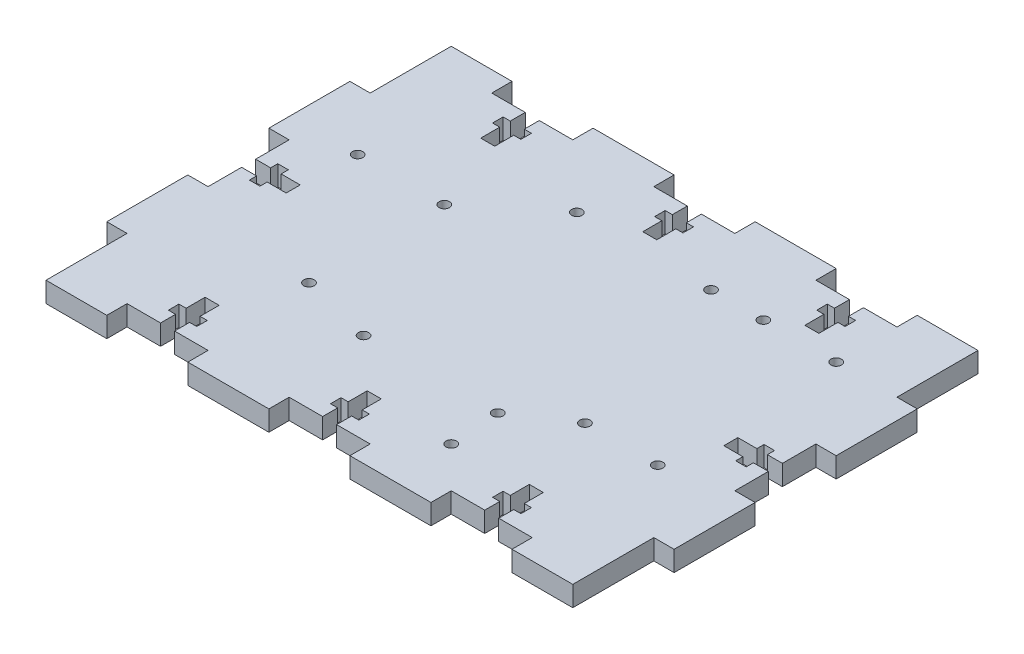
SolidWorks part; units mm, degrees
ref_plane "Front Plane" through (0, 0, 0) normal (0, 0, 1) x (1, 0, 0)
ref_plane "Top Plane" through (0, 0, 0) normal (0, 1, 0) x (1, 0, 0)
ref_plane "Right Plane" through (0, 0, 0) normal (1, 0, 0) x (0, 0, -1)
sketch "Sketch1" plane through (0, 0, 0) normal (0, 1, 0) x (1, 0, 0)
  line L1 (0, 0) -> (177.8, 0)
  line L2 (0, 0) -> (0, 127)
  line L3 (0, 127) -> (177.8, 127)
  line L4 (177.8, 0) -> (177.8, 127)
  dimension "D1" = 127
  dimension "D2" = 177.8
extrude "Boss-Extrude1" add sketch "Sketch1" along normal blind 6.35
sketch "Sketch2" plane through (0, 6.35, 0) normal (0, 1, 0) x (1, 0, 0)
  line L1 (0, 127) -> (6.35, 127)
  line L2 (0, 127) -> (0, 101.6)
  line L3 (0, 101.6) -> (6.35, 101.6)
  line L4 (6.35, 127) -> (6.35, 101.6)
  dimension "D1" = 25.4
  dimension "D2" = 6.35
extrude "Cut-Extrude1" cut sketch "Sketch2" against normal blind 6.35
pattern_linear "LPattern1" count 3 spacing 50.8 along (0, 0, 1) count 2 spacing 171.45 along (1, 0, 0) of "Cut-Extrude1"
sketch "Sketch3" plane through (0, 6.35, 0) normal (0, 1, 0) x (1, 0, 0)
  line L0 (6.35, 0) -> (171.45, 0) construction
  line L1 (25.4, 0) -> (50.8, 0)
  line L2 (25.4, 0) -> (25.4, 6.35)
  line L3 (25.4, 6.35) -> (50.8, 6.35)
  line L4 (50.8, 0) -> (50.8, 6.35)
  line L5 (0, 50.8) -> (0, 25.4) construction
  dimension "D1" = 25.4
  dimension "D2" = 6.35
  dimension "D3" = 25.4
extrude "Cut-Extrude2" cut sketch "Sketch3" against normal blind 6.35
pattern_linear "LPattern2" count 3 spacing 50.8 along (1, 0, 0) count 2 spacing 120.65 along (0, 0, -1) of "Cut-Extrude2"
ref_plane "Plane1" through (0, 0, -63.5) normal (0, 0, 1) x (1, 0, 0)
ref_plane "Plane2" through (88.9, 0, 0) normal (1, 0, 0) x (0, 0, -1)
sketch "Sketch4" plane through (0, 6.35, 0) normal (0, 1, 0) x (1, 0, 0)
  line L0 (171.45, 76.2) -> (171.45, 50.8) construction
  line L1 (171.45, 65.6971) -> (157.48, 65.6971)
  line L2 (171.45, 65.6971) -> (171.45, 61.3029)
  line L3 (171.45, 61.3029) -> (157.48, 61.3029)
  line L4 (157.48, 65.6971) -> (157.48, 61.3029)
  line L5 (177.8, 76.2) -> (171.45, 76.2) construction
  line L7 (163.449, 67.945) -> (166.751, 67.945)
  line L8 (163.449, 67.945) -> (163.449, 59.055)
  line L9 (163.449, 59.055) -> (166.751, 59.055)
  line L10 (166.751, 67.945) -> (166.751, 59.055)
  point P6 (171.45, 63.5)
  point P13 (165.1, 59.055)
  point P14 (166.751, 63.5)
  dimension "D1" = 13.97
  dimension "D2" = 4.3942
  dimension "D3" = 12.7
  dimension "D4" = 3.302
  dimension "D5" = 6.35
  dimension "D6" = 8.89
  dimension "D7" = 12.7
extrude "Cut-Extrude3" cut sketch "Sketch4" against normal blind 8.89 contours L1 L4 L3 L2 | L7 L10 L9 L8
mirror "Mirror1" about plane through (88.9, 0, 0) normal (1, 0, 0) of "Cut-Extrude3"
sketch "Sketch5" plane through (0, 6.35, 0) normal (0, 1, 0) x (1, 0, 0)
  line L0 (50.8, 6.35) -> (25.4, 6.35) construction
  line L1 (35.9029, 6.35) -> (40.2971, 6.35)
  line L2 (35.9029, 6.35) -> (35.9029, 20.32)
  line L3 (35.9029, 20.32) -> (40.2971, 20.32)
  line L4 (40.2971, 6.35) -> (40.2971, 20.32)
  line L5 (50.8, 0) -> (50.8, 6.35) construction
  line L6 (33.655, 14.351) -> (42.545, 14.351)
  line L7 (33.655, 14.351) -> (33.655, 11.049)
  line L8 (33.655, 11.049) -> (42.545, 11.049)
  line L9 (42.545, 14.351) -> (42.545, 11.049)
  point P6 (38.1, 20.32)
  point P12 (38.1, 11.049)
  point P15 (42.545, 12.7)
  dimension "D1" = 13.97
  dimension "D2" = 4.3942
  dimension "D3" = 12.7
  dimension "D4" = 3.302
  dimension "D5" = 8.89
  dimension "D6" = 12.7
  dimension "D7" = 6.35
extrude "Cut-Extrude4" cut sketch "Sketch5" against normal blind 30.48 contours L3 L4 L1 L2 | L7 L8 L9 L6
pattern_linear "LPattern3" count 3 spacing 50.8 along (1, 0, 0) of "Cut-Extrude4"
sketch "Sketch10" plane through (0, 6.35, 0) normal (0, 1, 0) x (1, 0, 0)
  line L0 (127, 120.65) -> (152.4, 120.65) construction
  line L1 (129.5908, 101.6) -> (152.4, 101.6)
  line L2 (129.5908, 101.6) -> (129.5908, 45.6692)
  line L3 (129.5908, 45.6692) -> (152.4, 45.6692)
  line L4 (152.4, 101.6) -> (152.4, 45.6692)
  line L6 (177.8, 76.2) -> (177.8, 101.6) construction
  dimension "D1" = 22.8092
  dimension "D2" = 55.9308
  dimension "D3" = 25.4
  dimension "D4" = 19.05
mirror "Mirror2" about plane through (0, 0, -63.5) normal (0, 0, 1) of "LPattern3"
hole_wizard "#4 Clearance Hole2" positions "Sketch12" profile "Sketch11" hole size "#4" standard "ANSI Inch"
sketch "Sketch12" plane through (0, 6.35, 0) normal (0, 1, 0) x (1, 0, 0)
  point P0 (129.5908, 101.6)
  point P3 (152.4, 101.6)
  point P6 (152.4, 45.6692)
  point P9 (129.5908, 45.6692)
sketch "Sketch11" plane through (129.5908, 6.35, -101.6) normal (1, 0, 0) x (0, 0, 1)
  line L0 (0, 0) -> (0, 11.1406)
  line L1 (0, 11.1406) -> (1.6319, 10.16)
  line L2 (1.6319, 10.16) -> (1.6319, 0)
  line L5 (1.6319, 0) -> (0, 0)
  line L10 (0, 11.1406) -> (-1.6319, 10.16) construction
  line L11 (0, -6.35) -> (0, 107.95) construction
  dimension "Hole Dia." = 3.2639
  dimension "Hole Depth" = 10.16
  dimension "Drill Angle" = 118
sketch "Sketch13" plane through (0, 6.35, 0) normal (0, 1, 0) x (1, 0, 0)
  line L0 (157.48, 65.6971) -> (157.48, 61.3029) construction
  line L1 (10.16, 90.551) -> (60.96, 90.551)
  line L2 (10.16, 90.551) -> (10.16, 36.449)
  line L3 (10.16, 36.449) -> (60.96, 36.449)
  line L4 (60.96, 90.551) -> (60.96, 36.449)
  line L5 (10.16, 90.551) -> (60.96, 36.449) construction
  line L6 (10.16, 36.449) -> (60.96, 90.551) construction
  line L8 (0, 101.6) -> (0, 76.2) construction
  point P0 (35.56, 63.5)
  point P7 (157.48, 63.5)
  point P8 (35.56, 90.551)
  dimension "D1" = 50.8
  dimension "D2" = 54.102
  dimension "D3" = 35.56
hole_wizard "#4 Clearance Hole3" positions "Sketch15" profile "Sketch14" hole size "#4" standard "ANSI Inch"
sketch "Sketch15" plane through (0, 6.35, 0) normal (0, 1, 0) x (1, 0, 0)
  line L0 (10.16, 90.551) -> (60.96, 90.551) construction
  line L3 (10.16, 90.551) -> (10.16, 36.449) construction
  point P0 (21.082, 82.931)
  point P2 (48.26, 82.931)
  point P4 (48.26, 40.513)
  dimension "D1" = 7.62
  dimension "D2" = 10.922
  dimension "D3" = 27.178
  dimension "D4" = 42.418
sketch "Sketch14" plane through (21.082, 6.35, -82.931) normal (1, 0, 0) x (0, 0, 1)
  line L0 (0, 0) -> (0, 11.1406)
  line L1 (0, 11.1406) -> (1.6319, 10.16)
  line L2 (1.6319, 10.16) -> (1.6319, 0)
  line L5 (1.6319, 0) -> (0, 0)
  line L10 (0, 11.1406) -> (-1.632, 10.16) construction
  line L11 (0, -6.35) -> (0, 107.95) construction
  dimension "Hole Dia." = 3.2639
  dimension "Hole Depth" = 10.16
  dimension "Drill Angle" = 118
hole_wizard "#4 Clearance Hole4" positions "Sketch18" profile "Sketch16" hole size "#4" standard "ANSI Inch"
sketch "Sketch18" plane through (0, 6.35, 0) normal (0, 1, 0) x (1, 0, 0)
  line L0 (177.8, 25.4) -> (177.8, 50.8) construction
  line L1 (137.5029, 6.35) -> (127, 6.35) construction
  point P0 (114.3, 19.05)
  dimension "D1" = 63.5
  dimension "D2" = 12.7
sketch "Sketch16" plane through (114.3, 6.35, -19.05) normal (1, 0, 0) x (0, 0, 1)
  line L0 (0, 0) -> (0, 11.1406)
  line L1 (0, 11.1406) -> (1.6319, 10.16)
  line L2 (1.6319, 10.16) -> (1.6319, 0)
  line L5 (1.6319, 0) -> (0, 0)
  line L10 (0, 11.1406) -> (-1.632, 10.16) construction
  line L11 (0, -6.35) -> (0, 107.95) construction
  dimension "Hole Dia." = 3.2639
  dimension "Hole Depth" = 10.16
  dimension "Drill Angle" = 118
hole_wizard "#4 Clearance Hole5" positions "Sketch20" profile "Sketch19" hole size "#4" standard "ANSI Inch"
sketch "Sketch20" plane through (0, 6.35, 0) normal (0, 1, 0) x (1, 0, 0)
  line L0 (0, 101.6) -> (0, 76.2) construction
  line L1 (76.2, 127) -> (50.8, 127) construction
  point P0 (71.12, 101.6)
  point P2 (113.1824, 101.6)
  point P4 (113.1824, 34.7472)
  point P6 (71.12, 34.7472)
  dimension "D1" = 71.12
  dimension "D2" = 42.0624
  dimension "D3" = 66.8528
  dimension "D4" = 25.4
sketch "Sketch19" plane through (71.12, 6.35, -101.6) normal (1, 0, 0) x (0, 0, 1)
  line L0 (0, 0) -> (0, 11.1406)
  line L1 (0, 11.1406) -> (1.6319, 10.16)
  line L2 (1.6319, 10.16) -> (1.6319, 0)
  line L5 (1.6319, 0) -> (0, 0)
  line L10 (0, 11.1406) -> (-1.6319, 10.16) construction
  line L11 (0, -6.35) -> (0, 107.95) construction
  dimension "Hole Dia." = 3.2639
  dimension "Hole Depth" = 10.16
  dimension "Drill Angle" = 118
